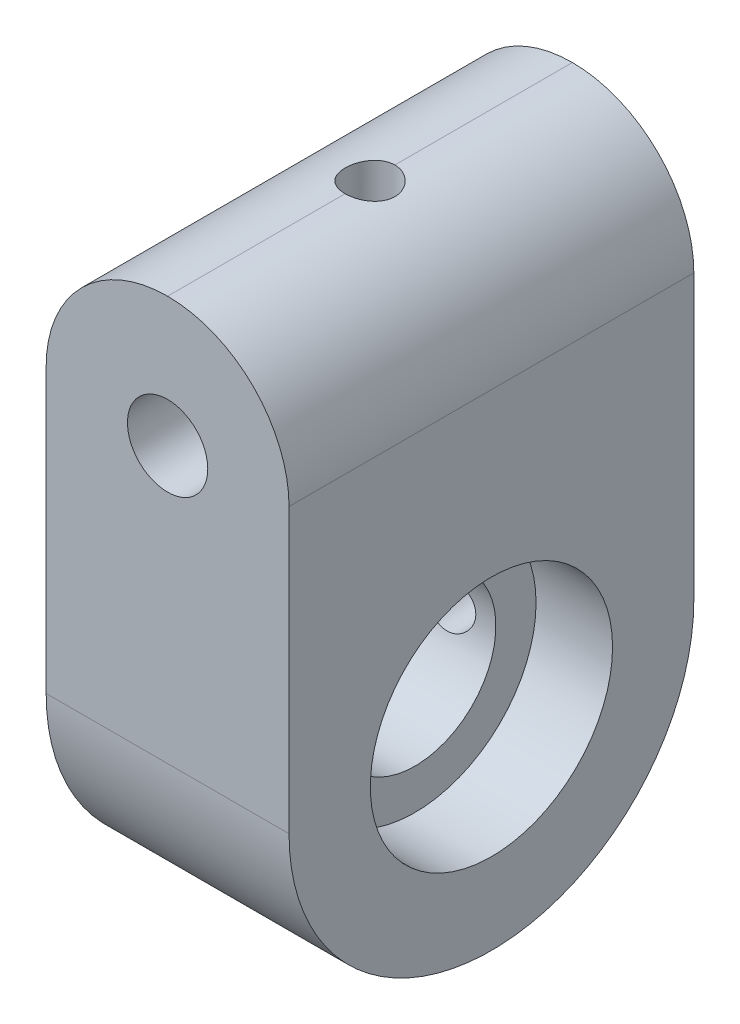
SolidWorks part; units mm, degrees
ref_plane "Front Plane" through (0, 0, 0) normal (0, 0, 1) x (1, 0, 0)
ref_plane "Top Plane" through (0, 0, 0) normal (0, 1, 0) x (1, 0, 0)
ref_plane "Right Plane" through (0, 0, 0) normal (1, 0, 0) x (0, 0, -1)
sketch "Sketch1" plane through (0, 0, 0) normal (1, 0, 0) x (0, 0, -1)
  circle A0 centre (0, 0) radius 9.5
  circle A1 centre (0, 0) radius 15.875
  dimension "D1" = 19
  dimension "D2" = 31.75
extrude "Boss-Extrude1" add sketch "Sketch1" along normal blind 6
sketch "Sketch2" plane through (0, 0, 0) normal (-1, 0, 0) x (0, 0, 1)
  circle A0 centre (0, 0) radius 6.35
  circle A1 centre (0, 0) radius 15.875
  circle A2 centre (0, 0) radius 15.875
  circle M3 centre (0, 0) radius 15.875
  circle M4 centre (0, 0) radius 9.5
  dimension "D2" = 12.7
  dimension "D1" = 0
extrude "Boss-Extrude2" add sketch "Sketch2" along normal blind 13.05 contours M3 M4 | A0 M4 region at (0, 0, -15.426) region at (0, 0, -9.2313)
sketch "Sketch3" plane through (-13.05, 0, 0) normal (-1, 0, 0) x (0, 0, 1)
  line L0 (0, 15.875) -> (0, -15.875) construction
  line L1 (0, 0) -> (19.648, 0) construction
  circle A0 centre (0, 12.7) radius 1.95
  circle A1 centre (0, 0) radius 15.875
  circle A2 centre (0, 0) radius 15.875
  circle A3 centre (0, -12.7) radius 1.95
  dimension "D2" = 3.9
  dimension "D3" = 12.7
  dimension "D1" = 0
extrude "Cut-Extrude1" cut sketch "Sketch3" against normal blind 10.16 contours A3 | A0 region at (-13.05, 12.7, 0) region at (-13.05, -12.7, 0)
ref_plane "Plane2" through (0, 0, -15.875) normal (0, 0, 1) x (1, 0, 0)
sketch "Sketch5" plane through (0, 0, -15.875) normal (0, 0, 1) x (1, 0, 0)
  line L0 (-13.05, 15.875) -> (-13.05, -15.875) construction
  line L1 (6, -15.875) -> (6, 15.875) construction
  line L2 (-13.05, 15.875) -> (-13.05, -15.875)
  line L3 (6, -15.875) -> (6, 15.875)
  line L4 (-13.05, 0) -> (6, 0) construction
  circle A0 centre (-3.525, 0) radius 1.95
  dimension "D1" = 3.9
extrude "Cut-Extrude3" cut sketch "Sketch5" along normal up to surface (9.525 mm away) contours A0 L4 | L4 A0 region at (-3.525, 0.8276, -15.875) region at (-3.525, -0.8276, -15.875) up to face at (-13.05, 0, 6.35)
sketch "Sketch6" plane through (-13.05, 0, 0) normal (-1, 0, 0) x (0, 0, 1)
  line L0 (0, 0) -> (0, 31.0805) construction
  line L1 (-15.875, 0) -> (-15.875, 31.75)
  line L2 (-15.875, 31.75) -> (15.875, 31.75)
  line L3 (15.875, 0) -> (15.875, 31.75)
  circle A1 centre (0, 0) radius 15.875
  circle A2 centre (0, 0) radius 15.875
  point P9 (0, 31.75)
  circle M6 centre (0, 0) radius 15.875
  dimension "D2" = 31.75
  dimension "D3" = 15.875
  dimension "D1" = 0
extrude "Boss-Extrude3" add sketch "Sketch6" against normal up to surface (19.05 mm away) contours L3 L2 L1 A2 M6 region at (-13.05, 21.7835, 0) up to face at (6, 0, -15.875)
sketch "Sketch7" plane through (0, 0, 15.875) normal (0, 0, 1) x (1, 0, 0)
  line L0 (6, 31.75) -> (-13.05, 31.75) construction
  line L1 (-3.525, 31.75) -> (-3.525, 21.59) construction
  line L2 (6, 0) -> (-13.05, 0) construction
  circle A0 centre (-3.525, 21.59) radius 3.15
  dimension "D1" = 6.3
  dimension "D2" = 21.59
extrude "Cut-Extrude4" cut sketch "Sketch7" against normal up to surface (31.75 mm away) contours A0 region at (-3.525, 21.59, 15.875) up to face at (-3.525, 10.5833, -15.875)
sketch "Sketch8" plane through (0, 31.75, 0) normal (0, 1, 0) x (1, 0, 0)
  line L0 (6, 15.875) -> (-13.05, 15.875) construction
  line L1 (-3.525, 15.875) -> (-3.525, 0) construction
  line L2 (-3.525, 0) -> (6, 0) construction
  line L3 (6, 15.875) -> (6, -15.875) construction
  circle A0 centre (-3.525, 0) radius 1.95
  dimension "D1" = 3.9
extrude "Cut-Extrude5" cut sketch "Sketch8" against normal up to surface (7.01 mm away) contours A0 region at (-3.525, 31.75, 0) up to face at (-0.375, 21.59, -15.875)
fillet "Fillet1" radius 9.525 2 edges at (6, 31.75, 0) (-13.05, 31.75, 0)
